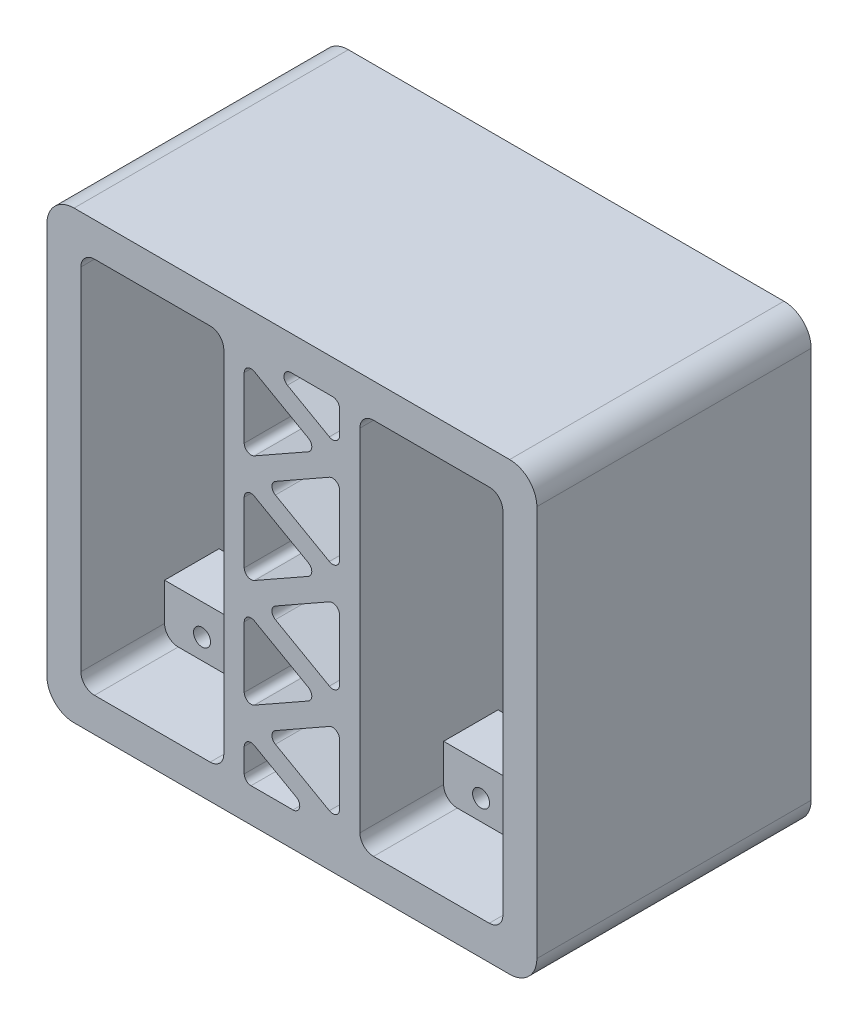
SolidWorks part; units mm, degrees
ref_plane "Front Plane" through (0, 0, 0) normal (0, 0, 1) x (1, 0, 0)
ref_plane "Top Plane" through (0, 0, 0) normal (0, 1, 0) x (1, 0, 0)
ref_plane "Right Plane" through (0, 0, 0) normal (1, 0, 0) x (0, 0, -1)
sketch "Sketch1" plane through (0, 0, 0) normal (0, 0, 1) x (1, 0, 0)
  line L0 (5, 60.5) -> (26, 60.5)
  line L1 (0, 0) -> (72, 0)
  line L2 (0, 0) -> (0, 65.5)
  line L3 (0, 65.5) -> (72, 65.5)
  line L4 (72, 0) -> (72, 65.5)
  line L5 (46, 60.5) -> (67, 60.5)
  line L6 (46, 60.5) -> (46, 5)
  line L7 (46, 5) -> (67, 5)
  line L8 (67, 60.5) -> (67, 5)
  line L9 (5, 60.5) -> (5, 5)
  line L10 (5, 5) -> (26, 5)
  line L12 (26, 60.5) -> (26, 5)
  line L13 (5, 53) -> (26, 53)
  line L14 (46, 53) -> (67, 53)
  line L15 (5, 12.5) -> (26, 12.5)
  line L16 (46, 12.5) -> (67, 12.5)
  line L17 (10.5, 57.5) -> (20.5, 57.5) construction
  line L18 (10.5, 8) -> (20.5, 8) construction
  line L19 (15.5, 57.5) -> (15.5, 8) construction
  line L20 (5, 32.75) -> (26, 32.75) construction
  line L21 (46, 32.75) -> (67, 32.75) construction
  line L22 (56.5, 57.5) -> (56.5, 8) construction
  line L23 (51.5, 57.5) -> (61.5, 57.5) construction
  line L24 (51.5, 8) -> (61.5, 8) construction
  circle A0 centre (10.5, 57.5) radius 1.25
  circle A1 centre (20.5, 57.5) radius 1.25
  circle A2 centre (10.5, 8) radius 1.25
  circle A3 centre (20.5, 8) radius 1.25
  circle A4 centre (51.5, 57.5) radius 1.25
  circle A5 centre (61.5, 57.5) radius 1.25
  circle A6 centre (61.5, 8) radius 1.25
  circle A7 centre (51.5, 8) radius 1.25
  point P33 (15.5, 32.75)
  point P34 (15.5, 32.75)
  point P41 (56.5, 32.75)
  point P42 (56.5, 32.75)
  point P49 (0, 0)
  point P50 (61.3945, 8)
  point P51 (62.1436, 8)
  point P52 (0, 0)
  point P53 (56.5, 8)
  point P54 (59.3522, 57.5)
  point P55 (56.5, 57.5)
  dimension "D13" = 2.5
  dimension "D1" = 21
  dimension "D2" = 5
  dimension "D3" = 55.5
  dimension "D4" = 55.5
  dimension "D5" = 21
  dimension "D6" = 5
  dimension "D7" = 5
  dimension "D8" = 20
  dimension "D9" = 5
  dimension "D10" = 7.5
  dimension "D11" = 7.5
  dimension "D12" = 10
  dimension "D15" = 49.5
extrude "Boss-Extrude2" add sketch "Sketch1" against normal blind 28 contours L1 L4 L3 L2 L5 L8 L7 L6 L0 L12 L10 L9 | L9 L13 L12 L0 | L15 L9 L10 L12 | L16 L6 L7 L8 | L6 L14 L8 L5 | A0 | A1 | A4 | A5 | A6 | A7 | A3 | A2 region at (15.5, 56.7001, 0) region at (15.5, 8.7999, 0) region at (36, 32.75, 0) region at (56.5, 56.7001, 0) region at (56.5, 8.7999, 0) region at (10.5, 57.5, 0) region at (20.5, 57.5, 0) region at (51.5, 57.5, 0) region at (61.5, 57.5, 0) region at (61.5, 8, 0) region at (51.5, 8, 0)
extrude "Boss-Extrude4" add sketch "Sketch1<4>" along normal blind 12.3 contours L1 L4 L3 L2 L5 L8 L7 L6 L0 L12 L10 L9 region at (36, 32.75, 0)
sketch "Sketch1<4>" plane through (0, 0, 0) normal (0, 0, 1) x (1, 0, 0) same geometry as "Sketch1"
fillet "Fillet2" radius 4 4 edges at (0, 0, -7.85) (72, 0, -7.85) (72, 65.5, -7.85) (0, 65.5, -7.85)
fillet "Fillet3" radius 2 8 edges at (46, 60.5, 6.15) (67, 5, 6.15) (67, 60.5, 6.15) (46, 5, 6.15) (5, 5, 6.15) (26, 5, 6.15) (26, 60.5, 6.15) (5, 60.5, 6.15)
extrude "Cut-Extrude1" cut sketch "Sketch1<5>" against normal blind 12 contours A0 | A2 | A3 | A7 | A6 | A4 | A1 | A5 region at (10.5, 57.5, 0) region at (10.5, 8, 0) region at (20.5, 8, 0) region at (51.5, 57.5, 0) region at (61.5, 8, 0) region at (51.5, 8, 0)
sketch "Sketch1<5>" plane through (0, 0, 0) normal (0, 0, 1) x (1, 0, 0) same geometry as "Sketch1"
sketch "Sketch5" plane through (0, 0, 12.3) normal (0, 0, 1) x (1, 0, 0)
  line L0 (28.2608, 59.1948) -> (39.9561, 52.5714)
  line L1 (26, 5) -> (46, 5)
  line L2 (26, 5) -> (26, 60.5)
  line L3 (26, 60.5) -> (46, 60.5)
  line L4 (46, 5) -> (46, 60.5)
  line L5 (26, 58.5) -> (26, 7) construction
  line L6 (46, 58.5) -> (46, 7) construction
  line L7 (7, 60.5) -> (24, 60.5) construction
  line L8 (7, 5) -> (24, 5) construction
  line L9 (29, 60.5) -> (43, 60.5)
  line L10 (43, 5) -> (43, 60.5)
  line L11 (29, 5) -> (43, 5)
  line L12 (29, 5) -> (29, 60.5)
  line L13 (29, 60.5) -> (43, 52.5714)
  line L14 (43, 52.5714) -> (29, 44.6429)
  line L15 (29, 44.6429) -> (43, 36.7143)
  line L16 (43, 36.7143) -> (29, 28.7857)
  line L17 (29, 28.7857) -> (43, 20.8571)
  line L18 (43, 20.8571) -> (29, 12.9286)
  line L19 (29, 12.9286) -> (43, 5)
  line L20 (39.9561, 52.5714) -> (25.9561, 44.6429)
  line L21 (25.9561, 44.6429) -> (39.9561, 36.7143)
  line L22 (39.9561, 36.7143) -> (25.9561, 28.7857)
  line L23 (25.9561, 28.7857) -> (39.9561, 20.8571)
  line L24 (39.9561, 20.8571) -> (25.9561, 12.9286)
  line L25 (25.9561, 12.9286) -> (42.2608, 3.6948)
  line L26 (29.7392, 61.8052) -> (46.0439, 52.5714)
  line L27 (46.0439, 52.5714) -> (32.0439, 44.6429)
  line L28 (32.0439, 44.6429) -> (46.0439, 36.7143)
  line L29 (46.0439, 36.7143) -> (32.0439, 28.7857)
  line L30 (32.0439, 28.7857) -> (46.0439, 20.8571)
  line L31 (46.0439, 20.8571) -> (32.0439, 12.9286)
  line L32 (32.0439, 12.9286) -> (43.7392, 6.3052)
  point P18 (28, 14.5221)
  point P23 (28, 9.7005)
  point P40 (42.4531, 8.5469)
  dimension "D2" = 1.5
  dimension "D1" = 3
  dimension "D4" = 3
  dimension "D3" = 1.5
extrude "Cut-Extrude2" cut sketch "Sketch5" against normal through all contours L20 L0 L12 | L9 L26 L10 | L27 L28 L10 | L22 L21 L12 | L29 L30 L10 | L24 L23 L12 | L31 L32 L10 | L25 L12 L11 region at (32.652, 52.5714, 12.3) region at (39.348, 58.4318, 12.3) region at (32.652, 36.7143, 12.3) region at (39.348, 44.6429, 12.3) region at (39.348, 28.7857, 12.3) region at (32.652, 20.8571, 12.3) region at (39.348, 12.9286, 12.3) region at (32.652, 7.0682, 12.3)
fillet "Fillet4" radius 1 24 edges at (39.9561, 5, -7.85) (29, 11.2047, -7.85) (29, 5, -7.85) (43, 6.7238, -7.85) (43, 19.1333, -7.85) (32.0439, 12.9286, -7.85) (29, 14.6524, -7.85) (29, 27.0619, -7.85) (39.9561, 20.8571, -7.85) (43, 22.581, -7.85) (43, 34.9904, -7.85) (32.0439, 28.7857, -7.85) (39.9561, 36.7143, -7.85) (29, 30.5096, -7.85) (29, 42.919, -7.85) (43, 38.4381, -7.85) (32.0439, 44.6429, -7.85) (43, 50.8476, -7.85) (29, 46.3667, -7.85) (39.9561, 52.5714, -7.85) (29, 58.7762, -7.85) (43, 54.2953, -7.85) (43, 60.5, -7.85) (32.0439, 60.5, -7.85)
sketch "Sketch8" plane through (0, 12.5, 0) normal (0, 1, 0) x (1, 0, 0)
  line L0 (26, 28) -> (26, 0) construction
  line L1 (5, 28) -> (26, 28)
  line L2 (5, 28) -> (5, 8)
  line L3 (5, 8) -> (26, 8)
  line L4 (26, 28) -> (26, 8)
  line L5 (46, 0) -> (67, 0) construction
  line L6 (46, 28) -> (67, 28)
  line L7 (46, 28) -> (46, 8)
  line L8 (46, 8) -> (67, 8)
  line L9 (67, 28) -> (67, 8)
  dimension "D1" = 8
extrude "Cut-Extrude8" cut sketch "Sketch8" against normal blind 10
ref_plane "Midplane" through (0, 32.75, 0) normal (0, 1, 0) x (1, 0, 0)
ref_plane "Plane2" through (56.5, 0, 0) normal (1, 0, 0) x (0, 0, -1)
ref_plane "Plane3" through (15.5, 0, 0) normal (1, 0, 0) x (0, 0, -1)
sketch "Sketch10" plane through (56.5, 0, 0) normal (1, 0, 0) x (0, 0, -1)
  line L0 (28, 2.5) -> (8, 2.5) construction
  line L1 (8, 2.5) -> (8, 12.5) construction
  line L2 (28, 2.5) -> (8, 2.5)
  line L3 (8, 2.5) -> (8, 12.5)
  line L4 (8, 12.5) -> (18, 2.5)
  point P5 (8, 12.8273)
  dimension "D1" = 45
extrude "Boss-Extrude5" add sketch "Sketch10" along normal blind 1.5 and the other way blind 1.5 contours L4 L3 L2 region at (56.5, 5.8333, -11.3333)
sketch "Sketch11" plane through (15.5, 0, 0) normal (1, 0, 0) x (0, 0, -1)
  line L0 (28, 2.5) -> (8, 2.5) construction
  line L1 (8, 2.5) -> (8, 12.5) construction
  line L2 (28, 2.5) -> (8, 2.5)
  line L3 (8, 2.5) -> (8, 12.5)
  line L4 (8, 12.5) -> (18, 2.5)
  dimension "D1" = 45
extrude "Boss-Extrude6" add sketch "Sketch11" along normal blind 1.5 and the other way blind 1.5 contours L4 L3 L2 region at (15.5, 5.8333, -11.3333)
mirror "Mirror2" about plane through (0, 32.75, 0) normal (0, 1, 0) of "Boss-Extrude6", "Boss-Extrude5", "Cut-Extrude8"
